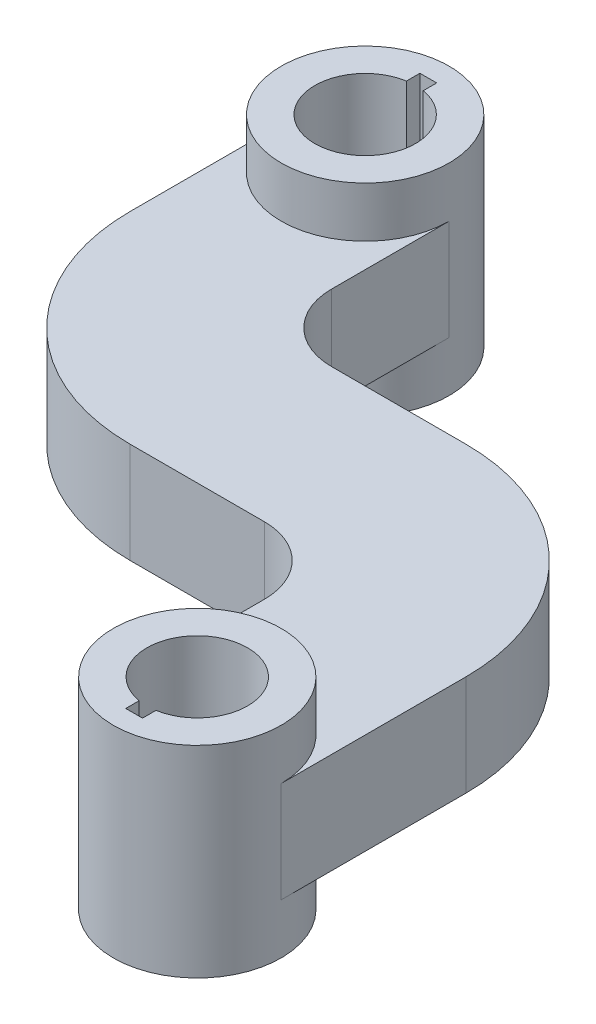
SolidWorks part; units mm, degrees
material "AISI 1045 Steel, cold drawn"
ref_plane "Front Plane" through (0, 0, 0) normal (0, 0, 1) x (1, 0, 0)
ref_plane "Top Plane" through (0, 0, 0) normal (0, 1, 0) x (1, 0, 0)
ref_plane "Right Plane" through (0, 0, 0) normal (1, 0, 0) x (0, 0, -1)
ref_axis "X-axis" through (-88.99, 0, 0) along (1, 0, 0)
ref_axis "Y-axis" through (0, 55, 0) along (0, -1, 0)
ref_axis "Z-axis" through (0, 0, -88.99) along (0, 0, 1)
sketch "Sketch1" plane through (0, 0, 0) normal (0, 1, 0) x (1, 0, 0)
  line L7 (0, -31.75) -> (-31.75, -31.75)
  line L8 (-107.95, 44.45) -> (-107.95, 101.6)
  line L10 (-44.45, 101.6) -> (-44.45, 57.15)
  line L11 (-19.05, 31.75) -> (0, 31.75)
  line L12 (0, 31.75) -> (31.75, 31.75)
  line L13 (107.95, -44.45) -> (107.95, -114.3)
  line L15 (44.45, -114.3) -> (44.45, -57.15)
  line L16 (19.05, -31.75) -> (0, -31.75)
  arc A0 (-107.95, 101.6) -> (-44.45, 101.6) centre (-76.2, 101.6) cw
  arc A1 (-44.45, 57.15) -> (-19.05, 31.75) centre (-19.05, 57.15) ccw
  arc A2 (-31.75, -31.75) -> (-107.95, 44.45) centre (-31.75, 44.45) cw
  arc A3 (44.45, -114.3) -> (107.95, -114.3) centre (76.2, -114.3) ccw
  arc A4 (31.75, 31.75) -> (107.95, -44.45) centre (31.75, -44.45) cw
  arc A5 (44.45, -57.15) -> (19.05, -31.75) centre (19.05, -57.15) ccw
  point P4 (0, 0)
  point P12 (-76.2, 133.35)
  dimension "D4" = 25.4
  dimension "D5" = 76.2
  dimension "D6" = 31.75
  dimension "D2" = 76.2
  dimension "D7" = 25.4
  dimension "D3" = 76.2
  dimension "D9" = 152.4
extrude "Boss-Extrude1" add sketch "Sketch1" along normal mid plane 38.1
sketch "Sketch2" plane through (0, 19.05, 0) normal (0, 1, 0) x (1, 0, 0)
  circle A0 centre (-76.2, 101.6) radius 31.75
  circle A1 centre (76.2, -114.3) radius 31.75
  arc A2 (-44.45, 101.6) -> (-107.95, 101.6) centre (-76.2, 101.6) ccw construction
  arc A3 (44.45, -114.3) -> (107.95, -114.3) centre (76.2, -114.3) ccw construction
extrude "Boss-Extrude2" add sketch "Sketch2" along normal blind 19.05 and the other way blind 57.15
sketch "Sketch3" plane through (0, 38.1, 0) normal (0, 1, 0) x (1, 0, 0)
  line L0 (-76.2, 101.6) -> (-76.2, 125.476) construction
  line L1 (-79.375, 125.476) -> (-73.025, 125.476)
  line L2 (-79.375, 125.476) -> (-79.375, 120.3836)
  line L3 (-73.025, 125.476) -> (-73.025, 120.3836)
  line L4 (76.2, -114.3) -> (76.2, -138.176) construction
  line L5 (73.025, -138.176) -> (79.375, -138.176)
  line L6 (73.025, -138.176) -> (73.025, -133.0836)
  line L7 (79.375, -138.176) -> (79.375, -133.0836)
  arc A0 (-79.375, 120.3836) -> (-73.025, 120.3836) centre (-76.2, 101.6) ccw
  arc A1 (79.375, -133.0836) -> (73.025, -133.0836) centre (76.2, -114.3) ccw
  point P6 (84.5048, -135.3136)
  point P10 (-76.2, 125.476)
  point P16 (76.2, -138.176)
  point P19 (67.9056, -135.3177)
  point P20 (-76.2, 128.5638)
  dimension "D1" = 38.1
  dimension "D2" = 6.35
  dimension "D3" = 23.876
extrude "Cut-Extrude1" cut sketch "Sketch3" against normal through all
